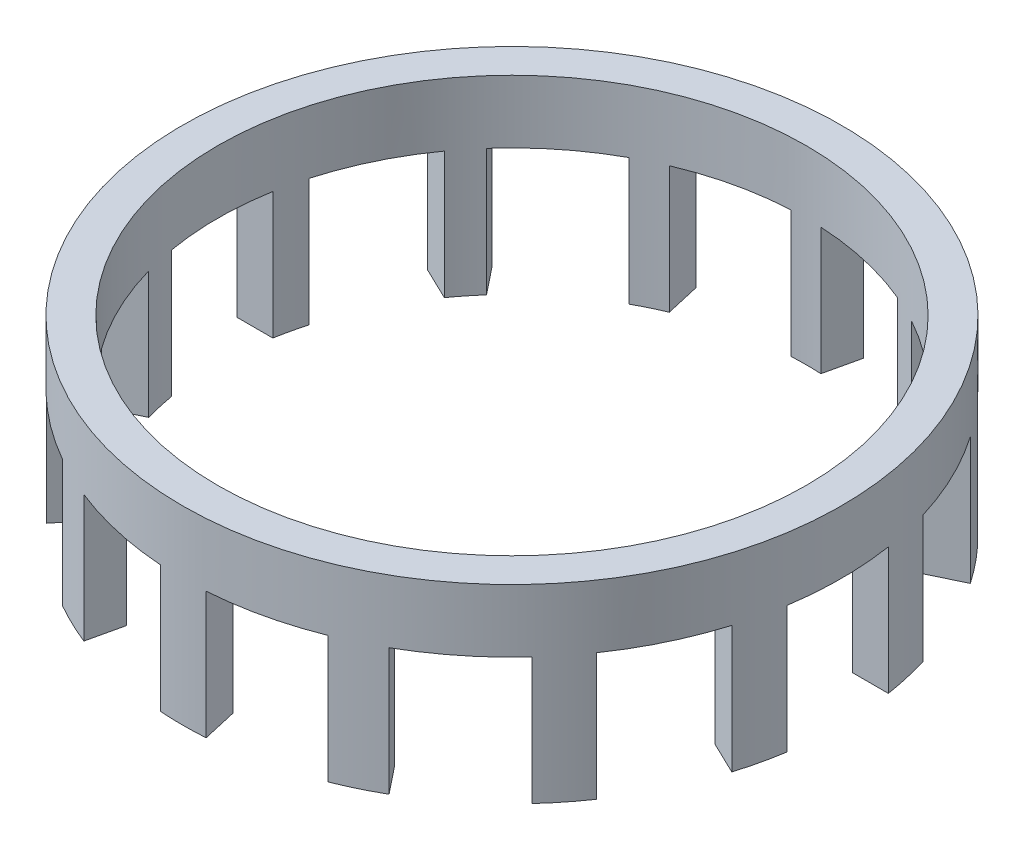
SolidWorks part; units mm, degrees
material "ABS"
ref_plane "Front Plane" through (0, 0, 0) normal (0, 0, 1) x (1, 0, 0)
ref_plane "Top Plane" through (0, 0, 0) normal (0, 1, 0) x (1, 0, 0)
ref_plane "Right Plane" through (0, 0, 0) normal (1, 0, 0) x (0, 0, -1)
sketch "Sketch1" plane through (0, 0, 0) normal (1, 0, 0) x (0, 0, -1)
  line L0 (-23.368, 20.5833) -> (-23.368, -4.3578) construction
  line L1 (0, 0) -> (-2.5, 0)
  line L2 (0, 0) -> (0, 13.462)
  line L3 (0, 13.462) -> (-2.5, 13.462)
  line L4 (-2.5, 0) -> (-2.5, 13.462)
  dimension "D1" = 13.462
  dimension "D2" = 2.5
  dimension "D3" = 23.368
revolve "Revolve1" add sketch "Sketch1" angle 360 about L0
sketch "Sketch2" plane through (0, 0, 0) normal (0, -1, 0) x (1, 0, 0)
  line L0 (0, 23.368) -> (-37.4405, 23.368) construction
  line L1 (-20.368, 19.768) -> (-20.368, 26.968)
  line L2 (-20.368, 26.968) -> (-23.089, 26.968)
  line L3 (-20.368, 19.768) -> (-23.089, 19.768)
  circle A1 centre (0, 23.368) radius 23.368 construction
  circle A2 centre (0, 23.368) radius 23.368
  point P9 (-20.368, 23.368)
  point P12 (-23.368, 23.368)
  circle M1 centre (0, 23.368) radius 23.368
  circle M2 centre (0, 23.368) radius 20.868
  dimension "D1" = 7.2
  dimension "D2" = 3
extrude "Cut-Extrude1" cut sketch "Sketch2" against normal blind 9 contours L0 L2 M2 M1 | L0 A2 L3 M2 region at (-22.0193, 0, 21.564) region at (-22.0193, 0, 25.172)
pattern_circular "CirPattern1" count 14 over 360 about axis through (0, 13.462, 23.368) along (0, 1, 0) of "Cut-Extrude1"
